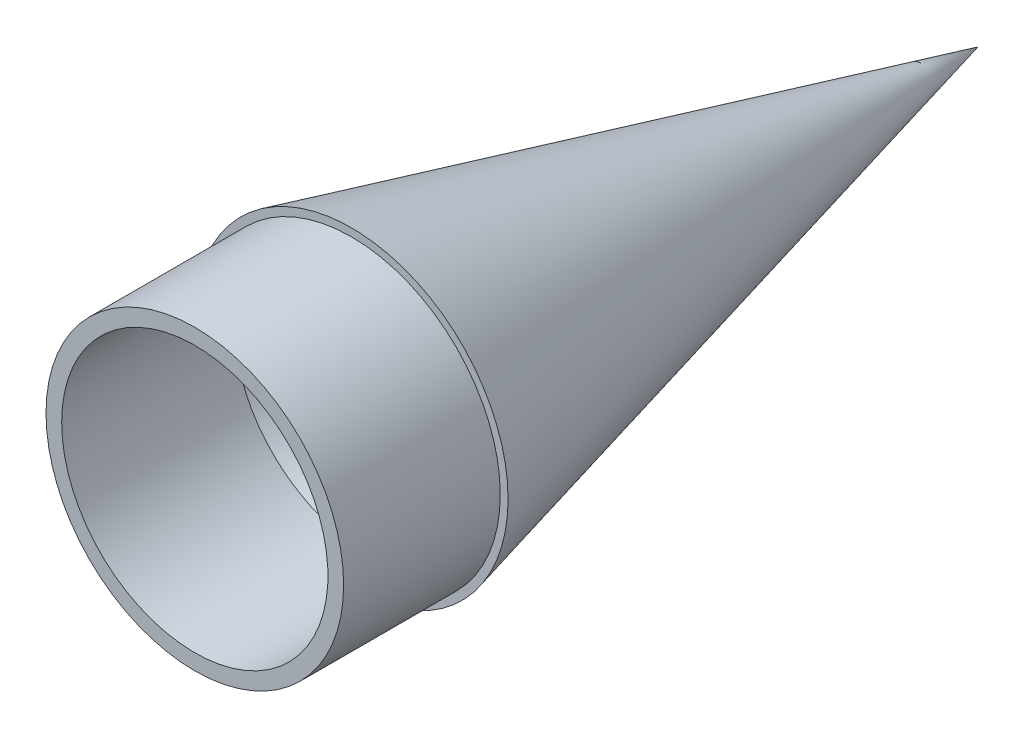
SolidWorks part; units mm, degrees
material "ABS"
ref_plane "Спереди" through (0, 0, 0) normal (0, 0, 1) x (1, 0, 0)
ref_plane "Сверху" through (0, 0, 0) normal (0, 1, 0) x (1, 0, 0)
ref_plane "Справа" through (0, 0, 0) normal (1, 0, 0) x (0, 0, -1)
sketch "Эскиз1" plane through (0, 0, 0) normal (0, 1, 0) x (1, 0, 0)
  line L0 (0, 0) -> (0, 80) construction
  line L1 (0, 0) -> (-20, 0) construction
  line L2 (0, 80) -> (-20, 0)
  line L3 (-20, 0) -> (-19, 0)
  line L4 (-19, 0) -> (-19, -20)
  line L5 (-17.7437, -20) -> (0, -20)
  line L6 (0, -20) -> (0, 80)
  line L7 (-17.7437, -20) -> (-19, -20)
  dimension "D1" = 20
  dimension "D2" = 1
  dimension "D3" = 20
  dimension "D4" = 19
  dimension "D5" = 100
revolve "Повернуть1" add sketch "Эскиз1" angle 360 about L6
shell "Оболочка1" thickness 2 removed face at (19, 0, 20)
